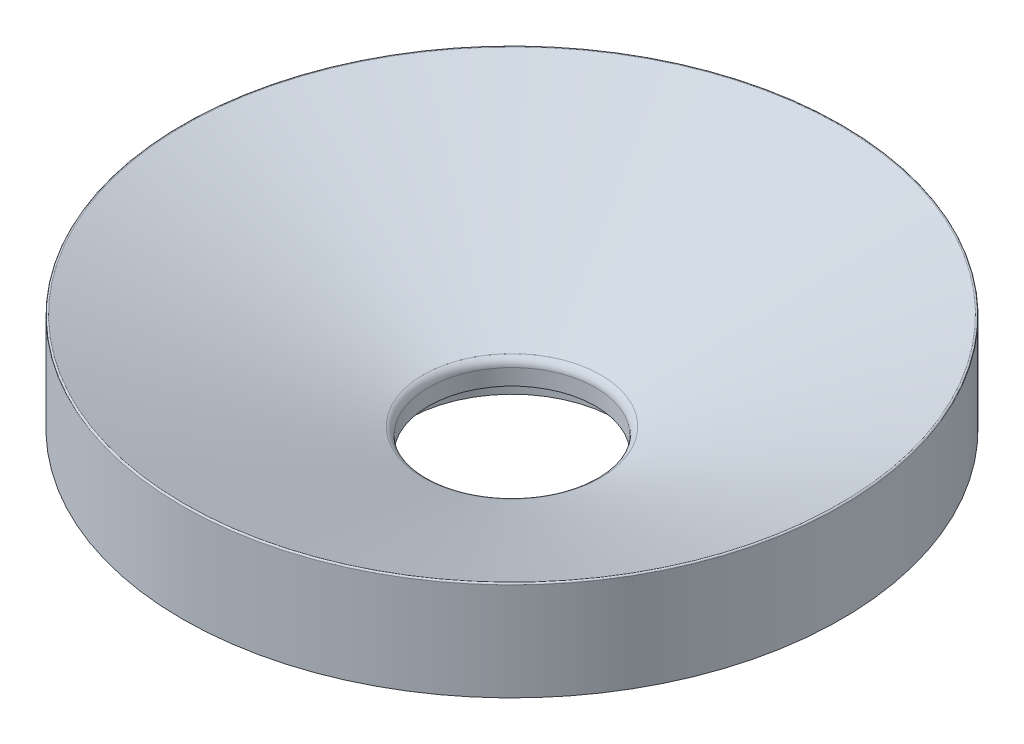
SolidWorks part; units mm, degrees
ref_plane "Front Plane" through (0, 0, 0) normal (0, 0, 1) x (1, 0, 0)
ref_plane "Top Plane" through (0, 0, 0) normal (0, 1, 0) x (1, 0, 0)
ref_plane "Right Plane" through (0, 0, 0) normal (1, 0, 0) x (0, 0, -1)
sketch "Sketch1" plane through (0, 0, 0) normal (0, 1, 0) x (1, 0, 0)
  circle A0 centre (0, 0) radius 15.113
  circle A1 centre (0, 0) radius 17.653
  dimension "D1" = 30.226
  dimension "D2" = 2.54
extrude "Boss-Extrude1" add sketch "Sketch1" along normal blind 3.175
sketch "Sketch2" plane through (0, 3.175, 0) normal (0, 1, 0) x (1, 0, 0)
  circle A0 centre (0, 0) radius 12.065
  circle A1 centre (0, 0) radius 17.653
  circle A2 centre (0, 0) radius 17.653 construction
  dimension "D1" = 24.13
extrude "Boss-Extrude2" add sketch "Sketch2" along normal blind 3.175
sketch "Sketch3" plane through (0, 6.35, 0) normal (0, 1, 0) x (1, 0, 0)
  circle A0 centre (0, 0) radius 12.065
  circle A1 centre (0, 0) radius 14.605
  dimension "D1" = 24.13
  dimension "D2" = 2.54
sketch "Sketch7" plane through (0, 6.35, 0) normal (0, 1, 0) x (1, 0, 0)
  circle A0 centre (0, 0) radius 47.625
  dimension "D1" = 95.25
  dimension "D2" = 0
extrude "Boss-Extrude3" add sketch "Sketch7" along normal blind 14.4196
ref_plane "Plane2" through (0, 0, -28.575) normal (0, 0, 1) x (1, 0, 0)
ref_axis "Axis1" through (0, 21.7921, -28.575) along (0, -1, 0)
sketch "Sketch8" plane through (0, 20.7696, 0) normal (0, 1, 0) x (1, 0, 0)
  circle A0 centre (0, 28.575) radius 46.355
  dimension "D1" = 92.71
loft "Cut-Loft1" cut section "Sketch3" section face at (0, 20.7696, 47.625) connector at (-1.5838, 6.35, 11.9606) connector at (-2.5299, 20.7696, 47.5578)
chamfer "Chamfer1" distance 2.54 angle 75 1 edges at (0, 6.35, 17.653) first distance on face at (0, 0, 17.653)
fillet "Fillet6" radius 1.27 1 edges at (0, 6.35, 12.065)
fillet "Fillet7" radius 0.1905 1 edges at (0, 20.7696, 47.625)
